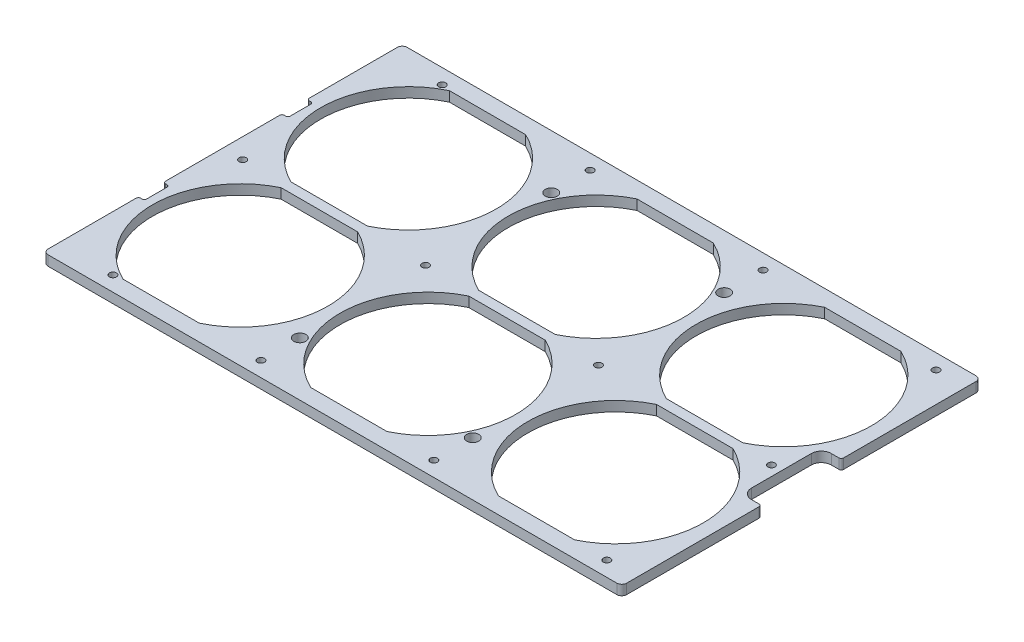
SolidWorks part; units mm, degrees
material "NEOPRENE"
ref_plane "Front" through (0, 0, 0) normal (0, 0, 1) x (1, 0, 0)
ref_plane "Top" through (0, 0, 0) normal (0, 1, 0) x (1, 0, 0)
ref_plane "Right" through (0, 0, 0) normal (1, 0, 0) x (0, 0, -1)
sketch "Sketch1" plane through (0, 0, 0) normal (0, 1, 0) x (1, 0, 0)
  line L0 (-24.3078, -3.1623) -> (24.3078, -3.1623)
  line L1 (-180.975, 114.3) -> (180.975, 114.3)
  line L2 (-184.15, 111.125) -> (-184.15, -111.125)
  line L3 (-180.975, -114.3) -> (180.975, -114.3)
  line L4 (184.15, 111.125) -> (184.15, -111.125)
  line L5 (-184.15, 114.3) -> (184.15, -114.3) construction
  line L6 (-184.15, -114.3) -> (184.15, 114.3) construction
  line L7 (95.1365, -3.1623) -> (143.7521, -3.1623)
  line L8 (95.1365, -3.1623) -> (95.1365, -103.8733) construction
  line L9 (95.1365, -103.8733) -> (143.7521, -103.8733)
  line L10 (143.7521, -3.1623) -> (143.7521, -103.8733) construction
  line L11 (95.1365, -3.1623) -> (143.7521, -103.8733) construction
  line L12 (95.1365, -103.8733) -> (143.7521, -3.1623) construction
  line L13 (-24.3078, -103.8733) -> (24.3078, -103.8733)
  line L14 (-143.7521, -3.1623) -> (-95.1365, -3.1623)
  line L15 (-143.7521, -103.8733) -> (-95.1365, -103.8733)
  line L16 (-24.3078, 103.8733) -> (24.3078, 103.8733)
  line L17 (-24.3078, 3.1623) -> (24.3078, 3.1623)
  line L18 (-143.7521, 103.8733) -> (-95.1365, 103.8733)
  line L19 (-143.7521, 3.1623) -> (-95.1365, 3.1623)
  line L20 (95.1365, 103.8733) -> (143.7521, 103.8733)
  line L21 (95.1365, 3.1623) -> (143.7521, 3.1623)
  line L22 (-95.1365, -103.8733) -> (-24.3078, -103.8733) construction
  line L23 (24.3078, -103.8733) -> (95.1365, -103.8733) construction
  line L24 (119.5086, 53.5178) -> (119.5086, -53.5178) construction
  line L25 (24.3078, 3.1623) -> (24.3078, -3.1623) construction
  line L26 (-175.3235, -53.5178) -> (-184.15, -53.5178) construction
  line L27 (175.3235, -53.5178) -> (184.15, -53.5178) construction
  line L28 (-24.3078, -103.8733) -> (-24.3078, -114.3) construction
  line L29 (-24.3078, 103.8733) -> (-24.3078, 114.3) construction
  arc A0 (95.1365, -3.1623) -> (95.1365, -103.8733) centre (119.5086, -53.5178) ccw
  arc A1 (143.7521, -3.1623) -> (143.7521, -103.8733) centre (119.38, -53.5178) cw
  arc A2 (-184.15, -111.125) -> (-180.975, -114.3) centre (-180.975, -111.125) ccw
  arc A3 (184.15, -111.125) -> (180.975, -114.3) centre (180.975, -111.125) cw
  arc A4 (184.15, 111.125) -> (180.975, 114.3) centre (180.975, 111.125) ccw
  arc A5 (-180.975, 114.3) -> (-184.15, 111.125) centre (-180.975, 111.125) ccw
  circle A6 centre (-149.225, -104.775) radius 2.2479 construction
  circle A8 centre (-55.0333, -104.775) radius 2.2479 construction
  arc A10 (-24.3078, -3.1623) -> (-24.3078, -103.8733) centre (0.0643, -53.5178) ccw
  arc A11 (24.3078, -3.1623) -> (24.3078, -103.8733) centre (-0.0643, -53.5178) cw
  arc A12 (-143.7521, -3.1623) -> (-143.7521, -103.8733) centre (-119.38, -53.5178) ccw
  arc A13 (-95.1365, -3.1623) -> (-95.1365, -103.8733) centre (-119.5086, -53.5178) cw
  arc A14 (-24.3078, 103.8733) -> (-24.3078, 3.1623) centre (0.0643, 53.5178) ccw
  arc A15 (24.3078, 103.8733) -> (24.3078, 3.1623) centre (-0.0643, 53.5178) cw
  arc A16 (-143.7521, 103.8733) -> (-143.7521, 3.1623) centre (-119.38, 53.5178) ccw
  arc A17 (-95.1365, 103.8733) -> (-95.1365, 3.1623) centre (-119.5086, 53.5178) cw
  arc A18 (95.1365, 103.8733) -> (95.1365, 3.1623) centre (119.5086, 53.5178) ccw
  arc A19 (143.7521, 103.8733) -> (143.7521, 3.1623) centre (119.38, 53.5178) cw
  circle A20 centre (55.0333, -104.775) radius 2.2479 construction
  circle A21 centre (165.1, -104.775) radius 2.2479 construction
  circle A22 centre (165.1, 104.775) radius 2.2479 construction
  circle A23 centre (55.0333, 104.775) radius 2.2479 construction
  circle A24 centre (-55.0333, 104.775) radius 2.2479 construction
  circle A25 centre (-149.225, 104.775) radius 2.2479 construction
  circle A26 centre (-149.225, -104.775) radius 2.2479
  circle A27 centre (-55.0333, -104.775) radius 2.2479
  circle A28 centre (55.0333, -104.775) radius 2.2479
  circle A29 centre (165.1, -104.775) radius 2.2479
  circle A30 centre (165.1, 104.775) radius 2.2479
  circle A31 centre (55.0333, 104.775) radius 2.2479
  circle A32 centre (-55.0333, 104.775) radius 2.2479
  circle A33 centre (-149.225, 104.775) radius 2.2479
  circle A34 centre (55.0291, 80.01) radius 1.8288 construction
  circle A35 centre (-55.0291, 80.01) radius 1.8288 construction
  circle A36 centre (-55.0333, 0) radius 2.2479 construction
  circle A37 centre (55.0333, 0) radius 2.2479 construction
  circle A38 centre (55.0291, -80.01) radius 1.8288 construction
  circle A39 centre (-55.0291, -80.01) radius 1.8288 construction
  circle A40 centre (55.0291, 80.01) radius 1.8288 construction
  circle A41 centre (-55.0291, 80.01) radius 1.8288 construction
  circle A42 centre (-55.0333, 0) radius 2.2479
  circle A43 centre (55.0333, 0) radius 2.2479
  circle A44 centre (55.0291, -80.01) radius 1.8288 construction
  circle A45 centre (-55.0291, -80.01) radius 1.8288 construction
  circle A46 centre (-55.0291, 80.01) radius 3.81
  circle A47 centre (-55.0291, -80.01) radius 3.81
  circle A48 centre (55.0291, -80.01) radius 3.81
  circle A49 centre (55.0291, 80.01) radius 3.81
  circle A50 centre (165.1, 0) radius 2.2479 construction
  circle A51 centre (165.1, 0) radius 2.2479
  circle A52 centre (-171.45, 0) radius 2.2479 construction
  circle A53 centre (-171.45, 0) radius 2.2479
  point P0 (0, 0)
  point P6 (119.4443, -53.5178)
  dimension "D4" = 111.887
  dimension "D8" = 3.175
  dimension "D9" = 7.62
  dimension "D1" = 368.3
  dimension "D2" = 228.6
  dimension "D3" = 100.711
  dimension "D5" = 48.6156
  dimension "D6" = 119.38
  dimension "D7" = 107.0356
  dimension "D11" = 3
  dimension "D12" = 2
extrude "Boss-Extrude1" add sketch "Sketch1" along normal blind 6.35
sketch "Sketch2" plane through (0, 6.35, 0) normal (0, 1, 0) x (1, 0, 0)
  line L0 (0, 0) -> (184.15, 0) construction
  line L1 (184.15, -111.125) -> (184.15, 111.125) construction
  line L2 (184.15, -111.125) -> (184.15, 111.125) construction
  line L3 (184.15, 25.4) -> (177.8, 25.4)
  line L4 (184.15, 25.4) -> (184.15, -25.4)
  line L5 (184.15, -25.4) -> (177.8, -25.4)
  line L6 (171.45, 19.05) -> (171.45, -19.05)
  arc A0 (177.8, -25.4) -> (171.45, -19.05) centre (177.8, -19.05) cw
  arc A1 (177.8, 25.4) -> (171.45, 19.05) centre (177.8, 19.05) ccw
  point P14 (171.45, -25.4)
  point P17 (171.45, 25.4)
  dimension "D3" = 6.35
  dimension "D1" = 12.7
  dimension "D2" = 50.8
extrude "Cut-Extrude1" cut sketch "Sketch2" against normal through all and the other way through all
sketch "Sketch3" plane through (0, 6.35, 0) normal (0, 1, 0) x (1, 0, 0)
  line L0 (-184.15, 111.125) -> (-184.15, -111.125) construction
  line L1 (-184.15, 53.6575) -> (-180.34, 53.6575)
  line L2 (-184.15, 53.6575) -> (-184.15, 37.7825)
  line L3 (-184.15, 37.7825) -> (-180.34, 37.7825)
  line L4 (-180.34, 53.6575) -> (-180.34, 37.7825)
  line L5 (-180.34, 45.72) -> (-184.15, 45.72) construction
  line L6 (0, 0) -> (-184.15, 0) construction
  line L8 (-184.15, -37.7825) -> (-180.34, -37.7825)
  line L9 (-180.34, -53.6575) -> (-180.34, -37.7825)
  line L10 (-184.15, -53.6575) -> (-180.34, -53.6575)
  line L11 (-184.15, -53.6575) -> (-184.15, -37.7825)
  dimension "D1" = 3.81
  dimension "D2" = 15.875
  dimension "D3" = 45.72
extrude "Cut-Extrude2" cut sketch "Sketch3" against normal through all
fillet "Fillet1" radius 1.524 10 edges at (184.15, 3.175, 25.4) (184.15, 3.175, -25.4) (-180.34, 3.175, 37.7825) (-184.15, 3.175, 37.7825) (-184.15, 3.175, 53.6575) (-180.34, 3.175, 53.6575) (-184.15, 3.175, -37.7825) (-180.34, 3.175, -37.7825) (-184.15, 3.175, -53.6575) (-180.34, 3.175, -53.6575)
